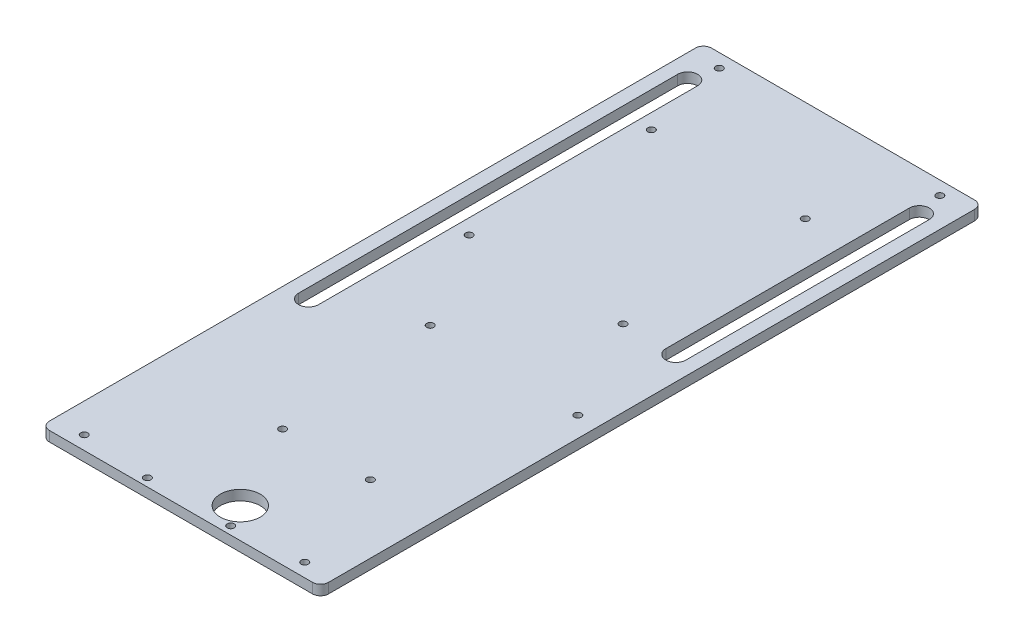
SolidWorks part; units mm, degrees
ref_plane "Front Plane" through (0, 0, 0) normal (0, 0, 1) x (1, 0, 0)
ref_plane "Top Plane" through (0, 0, 0) normal (0, 1, 0) x (1, 0, 0)
ref_plane "Right Plane" through (0, 0, 0) normal (1, 0, 0) x (0, 0, -1)
sketch "Sketch2" plane through (0, 0, 0) normal (0, 0, 1) x (1, 0, 0)
  line L0 (42.8242, -21.393) -> (42.8242, -24.5934)
  line L1 (0, -21.393) -> (0, -24.5934) construction
  line L2 (-46.0758, -24.5934) -> (42.8242, -24.5934)
  line L3 (-46.0758, -21.393) -> (-46.0758, -24.5934)
  line L4 (-46.0758, -21.393) -> (42.8242, -21.393)
  dimension "D1" = 88.9
  dimension "D2" = 3.2004
extrude "Boss-Extrude1" add sketch "Sketch2" along normal blind 210.82 contours L2 L0 L4 L3
sketch "Sketch3" plane through (0, -21.393, 0) normal (0, 1, 0) x (-1, 0, 0)
  line L0 (-42.8242, 208.28) -> (46.0758, 208.28) construction
  line L1 (38.5043, 9.421) -> (38.5043, 0) construction
  line L2 (46.0758, 0) -> (-42.8242, 0) construction
  line L3 (46.0758, 210.82) -> (-42.8242, 210.82) construction
  line L4 (36.73, 206.502) -> (46.0758, 206.502) construction
  line L5 (46.0758, 72.9493) -> (41.6793, 72.9493) construction
  line L6 (35.3293, 12.596) -> (41.6793, 12.596) construction
  line L7 (35.3293, 12.596) -> (35.3293, 133.3026)
  line L8 (35.3293, 133.3026) -> (41.6793, 133.3026) construction
  line L9 (41.6793, 12.596) -> (41.6793, 133.3026)
  line L10 (46.0758, 210.82) -> (-42.8242, 210.82) construction
  line L11 (-11.6838, 208.28) -> (-11.6838, 210.82) construction
  line L12 (-11.6838, 201.168) -> (-11.6838, 208.28) construction
  line L13 (-7.6198, 201.168) -> (-11.6838, 201.168) construction
  line L14 (-42.8242, 210.82) -> (-42.8242, 0) construction
  line L15 (46.0758, 210.82) -> (46.0758, 0) construction
  line L16 (-33.4785, 206.502) -> (-33.4785, 210.82) construction
  line L17 (-33.4785, 206.502) -> (-42.8242, 206.502) construction
  line L18 (36.73, 206.502) -> (36.73, 210.82) construction
  line L19 (-33.4785, 4.318) -> (-42.8242, 4.318) construction
  line L20 (-33.4785, 4.318) -> (-33.4785, 0) construction
  line L21 (46.0758, 0) -> (-42.8242, 0) construction
  line L22 (36.73, 4.318) -> (36.73, 0) construction
  line L23 (36.73, 4.318) -> (46.0758, 4.318) construction
  line L24 (-18.451, 32.1211) -> (-18.451, 0) construction
  line L25 (-42.8242, 32.1211) -> (-18.451, 32.1211) construction
  line L26 (-18.451, 32.1211) -> (30.549, 32.1211) construction
  line L27 (-18.451, 32.1211) -> (-18.451, 90.1211) construction
  line L28 (30.549, 32.1211) -> (30.549, 90.1211) construction
  line L29 (-18.451, 90.1211) -> (30.549, 90.1211) construction
  line L30 (-42.8242, 122.5046) -> (-36.4214, 122.5046) construction
  line L31 (-36.4214, 122.5046) -> (-36.4214, 0) construction
  line L33 (-21.1814, 173.3046) -> (6.7586, 173.3046) construction
  line L34 (60.367, -163.7177) -> (66.7698, -163.7177) construction
  line L35 (66.7698, -163.7177) -> (96.7645, -163.7177) construction
  line L36 (-36.4214, 121.2346) -> (11.8386, 121.2346) construction
  line L37 (81.5791, -113.2668) -> (108.3182, -113.2668) construction
  line L38 (81.5791, -113.2668) -> (66.7698, -163.7177) construction
  line L39 (76.3923, -158.9273) -> (82.7952, -158.9273) construction
  line L40 (82.7952, -158.9273) -> (112.7898, -158.9273) construction
  line L41 (97.6044, -108.4763) -> (124.3436, -108.4763) construction
  line L42 (97.6044, -108.4763) -> (82.7952, -158.9273) construction
  line L43 (-36.4214, 121.2346) -> (-36.4214, 173.3046) construction
  line L44 (-36.4214, 173.3046) -> (11.8386, 173.3046) construction
  line L45 (11.8386, 121.2346) -> (11.8386, 173.3046) construction
  line L46 (-32.0777, 12.596) -> (-38.4277, 12.596) construction
  line L47 (-32.0777, 12.596) -> (-32.0777, 90.1226)
  line L48 (-32.0777, 90.1226) -> (-38.4277, 90.1226) construction
  line L49 (-38.4277, 12.596) -> (-38.4277, 90.1226)
  circle A0 centre (14.8338, 208.28) radius 1.1303
  arc A1 (35.3293, 133.3026) -> (41.6793, 133.3026) centre (38.5043, 133.3026) cw
  arc A2 (41.6793, 12.596) -> (35.3293, 12.596) centre (38.5043, 12.596) cw
  circle A3 centre (-11.6838, 208.28) radius 1.1303
  circle A4 centre (-7.6198, 201.168) radius 6.35
  circle A5 centre (-33.4785, 206.502) radius 1.1303
  circle A6 centre (36.73, 206.502) radius 1.1303
  circle A7 centre (-33.4785, 4.318) radius 1.1303
  circle A8 centre (36.73, 4.318) radius 1.1303
  circle A9 centre (-18.451, 32.1211) radius 1.1303
  circle A10 centre (-18.451, 90.1211) radius 1.1303
  circle A11 centre (30.549, 90.1211) radius 1.1303
  circle A12 centre (30.549, 32.1211) radius 1.1303
  circle A13 centre (-21.1814, 173.3046) radius 1.1303
  circle A14 centre (-36.4214, 122.5046) radius 1.1303
  circle A15 centre (6.7586, 173.3046) radius 1.1303
  circle A16 centre (11.8386, 121.2346) radius 1.1303
  circle A17 centre (81.5791, -113.2668) radius 1.1303
  circle A18 centre (66.7698, -163.7177) radius 1.1303
  circle A19 centre (108.3182, -113.2668) radius 1.1303
  circle A20 centre (97.6044, -108.4763) radius 1.1303
  circle A21 centre (82.7952, -158.9273) radius 1.1303
  circle A22 centre (124.3436, -108.4763) radius 1.1303
  circle A23 centre (112.7898, -158.9273) radius 1.1303
  arc A24 (-32.0777, 12.596) -> (-38.4277, 12.596) centre (-35.2527, 12.596) cw
  arc A25 (-38.4277, 90.1226) -> (-32.0777, 90.1226) centre (-35.2527, 90.1226) cw
  point P12 (1.6258, 208.28)
  dimension "D5" = 2.2606
  dimension "D9" = 12.7
  dimension "D13" = 2.2606
  dimension "D15" = 9.3458
  dimension "D2" = 4.3965
  dimension "D3" = 120.7066
  dimension "D4" = 6.35
  dimension "D6" = 2.54
  dimension "D7" = 26.5176
  dimension "D8" = 13.208
  dimension "D10" = 7.112
  dimension "D11" = 4.064
  dimension "D12" = 9.421
  dimension "D14" = 4.318
  dimension "D16" = 24.3732
  dimension "D17" = 32.1211
  dimension "D18" = 49
  dimension "D19" = 58
  dimension "D20" = 6.4028
  dimension "D21" = 122.5046
  dimension "D22" = 52.07
  dimension "D23" = 1.27
  dimension "D24" = 27.94
  dimension "D25" = 15.24
  dimension "D26" = 6.4028
  dimension "D27" = 29.9946
  dimension "D28" = 26.7391
  dimension "D29" = 73.641
  dimension "D30" = 52.5796
  dimension "D31" = 6.4028
  dimension "D32" = 29.9946
  dimension "D33" = 26.7391
  dimension "D34" = 73.641
  dimension "D35" = 52.5796
  dimension "D36" = 48.26
  dimension "D37" = 77.5266
extrude "Cut-Extrude1" cut sketch "Sketch3" against normal through all
sketch "Sketch4" plane through (0, 0, 0) normal (0, 0, -1) x (-1, 0, 0)
  line L0 (1.6258, -21.393) -> (1.6258, -24.5934) construction
  line L1 (46.0758, -21.393) -> (-42.8242, -21.393) construction
  line L2 (46.0758, -24.5934) -> (-42.8242, -24.5934) construction
sketch "Sketch5" plane through (42.8242, 0, 0) normal (1, 0, 0) x (0, 0, -1)
  line L0 (-105.41, -21.393) -> (-105.41, -24.5934) construction
  line L1 (-210.82, -21.393) -> (0, -21.393) construction
  line L2 (-210.82, -24.5934) -> (0, -24.5934) construction
fillet "Fillet2" radius 2.54 4 edges at (42.8242, -22.9932, 210.82) (-46.0758, -22.9932, 210.82) (-46.0758, -22.9932, 0) (42.8242, -22.9932, 0)
